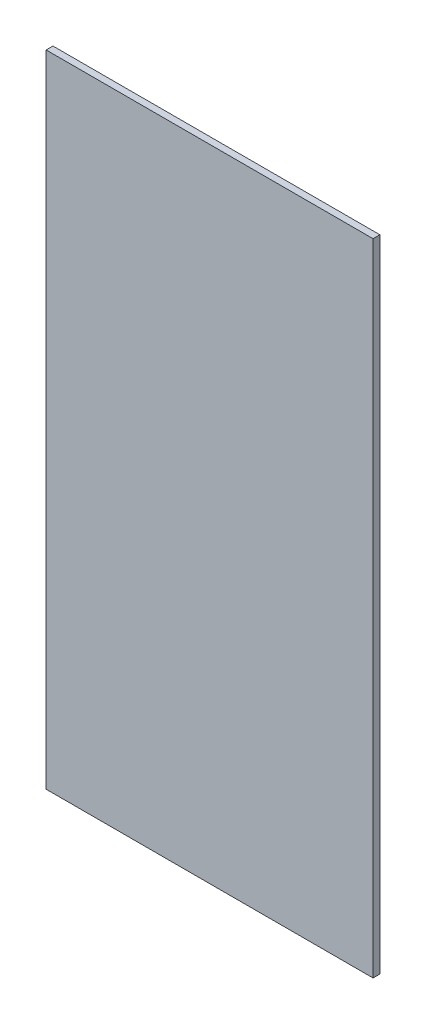
SolidWorks part; units mm, degrees
material "PC High Viscosity"
ref_plane "Front Plane" through (0, 0, 0) normal (0, 0, 1) x (1, 0, 0)
ref_plane "Top Plane" through (0, 0, 0) normal (0, 1, 0) x (1, 0, 0)
ref_plane "Right Plane" through (0, 0, 0) normal (1, 0, 0) x (0, 0, -1)
sketch "Sketch1" plane through (0, 0, 0) normal (0, 0, 1) x (1, 0, 0)
  line L1 (-304.8, 596.9) -> (0, 596.9)
  line L2 (-304.8, 596.9) -> (-304.8, 0)
  line L3 (-304.8, 0) -> (0, 0)
  line L4 (0, 596.9) -> (0, 0)
  dimension "D1" = 596.9
  dimension "D2" = 304.8
extrude "Boss-Extrude1" add sketch "Sketch1" along normal blind 6.35
